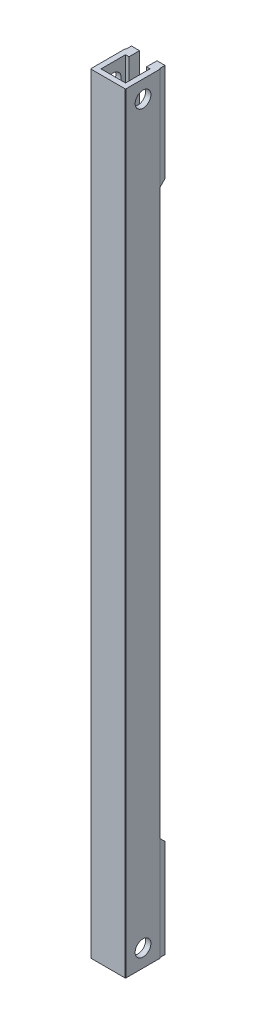
SolidWorks part; units mm, degrees
ref_plane "Front Plane" through (0, 0, 0) normal (0, 0, 1) x (1, 0, 0)
ref_plane "Top Plane" through (0, 0, 0) normal (0, 1, 0) x (1, 0, 0)
ref_plane "Right Plane" through (0, 0, 0) normal (1, 0, 0) x (0, 0, -1)
sketch "Sketch1" plane through (0, 0, 0) normal (0, 1, 0) x (1, 0, 0)
  line L1 (5, -5) -> (-5, -5)
  line L2 (5, -5) -> (5, 5)
  line L3 (5, 5) -> (-5, 5)
  line L4 (-5, -5) -> (-5, 5)
  line L5 (5, -5) -> (-5, 5) construction
  line L6 (5, 5) -> (-5, -5) construction
  point P0 (0, 0)
  dimension "D1" = 10
extrude "Extrude-Thin1" add sketch "Sketch1" along normal blind 220 thin thin type one direction reverse wall 1.5
sketch "Sketch2" plane through (0, 0, 0) normal (1, 0, 0) x (0, 0, -1)
  line L0 (-5, 110) -> (-50005, 110) construction
  line L1 (-5, 220) -> (-5, 0) construction
  line L2 (0, 0) -> (0, 50000) construction
  line L3 (-5, 220) -> (5, 220) construction
  line L4 (0, 220) -> (0, -49780) construction
  circle A0 centre (0, 215) radius 2.25
  circle A1 centre (0, 5) radius 2.25
  point P4 (-5, 110)
  dimension "D1" = 4.5
  dimension "D2" = 5
extrude "Cut-Extrude1" cut sketch "Sketch2" against normal through all both and the other way through all
fillet "Fillet1" radius 0.2 4 edges at (-5, 110, 5) (5, 110, 5) (-5, 110, -5) (5, 110, -5)
sketch "Sketch5" plane through (0, 0, -5) normal (0, 0, -1) x (-1, 0, 0)
  line L0 (0, 220) -> (0, -49780) construction
  line L1 (-4.8, 220) -> (4.8, 220) construction
  line L2 (-4.8, 110) -> (-50004.8, 110) construction
  line L3 (-4.8, 220) -> (-4.8, 0) construction
  line L4 (5, 192.5) -> (5, 220)
  line L5 (2.5, 195) -> (-2.5, 195)
  line L6 (2.5, 195) -> (2.5, 220)
  line L7 (2.5, 220) -> (-2.5, 220)
  line L8 (-2.5, 195) -> (-2.5, 220)
  line L9 (2.5, 195) -> (-2.5, 220) construction
  line L10 (2.5, 220) -> (-2.5, 195) construction
  line L11 (5, 192.5) -> (-5, 192.5)
  line L12 (-5, 192.5) -> (-5, 220)
  line L13 (2.5, 220) -> (5, 220)
  line L14 (-2.5, 220) -> (-5, 220)
  line L15 (2.5, 0) -> (-2.5, 25) construction
  line L16 (2.5, 25) -> (-2.5, 0) construction
  line L17 (0, 0) -> (0, 50000) construction
  line L18 (-2.5, 0) -> (-5, 0)
  line L19 (2.5, 0) -> (5, 0)
  line L20 (-5, 27.5) -> (-5, 0)
  line L21 (5, 27.5) -> (-5, 27.5)
  line L22 (-2.5, 25) -> (-2.5, 0)
  line L23 (2.5, 0) -> (-2.5, 0)
  line L24 (2.5, 25) -> (2.5, 0)
  line L25 (2.5, 25) -> (-2.5, 25)
  line L26 (5, 27.5) -> (5, 0)
  point P4 (0, 220)
  point P9 (-4.8, 110)
  point P10 (0, 207.5)
  point P25 (0, 12.5)
  line M6 (-4.8, 0) -> (4.8, 0)
  line M7 (4.8, 0) -> (4.8, 220)
  line M8 (4.8, 220) -> (-4.8, 220)
  line M9 (-4.8, 220) -> (-4.8, 0)
  dimension "D1" = 25
  dimension "D2" = 5
  dimension "D3" = 2.5
extrude "Cut-Extrude2" cut sketch "Sketch5" against normal up to next contours L8 L5 L6 M8 | L24 L25 L22 M6 region at (0, 207.5, -5) region at (0, 12.5, -5)
extrude "Boss-Extrude3" add sketch "Sketch5<3>" along normal blind 1.5 contours L25 L24 L21 L22 M6 M7 M9 | L11 L6 L5 L8 M7 M8 M9 region at (0, 192.7913, -5) region at (-4.5087, 13.75, -5)
sketch "Sketch5<3>" plane through (0, 0, -5) normal (0, 0, -1) x (-1, 0, 0) same geometry as "Sketch5"
chamfer "Chamfer1" distance 2 angle 45 2 edges at (0, 27.5, -5) (0, 192.5, -5)
